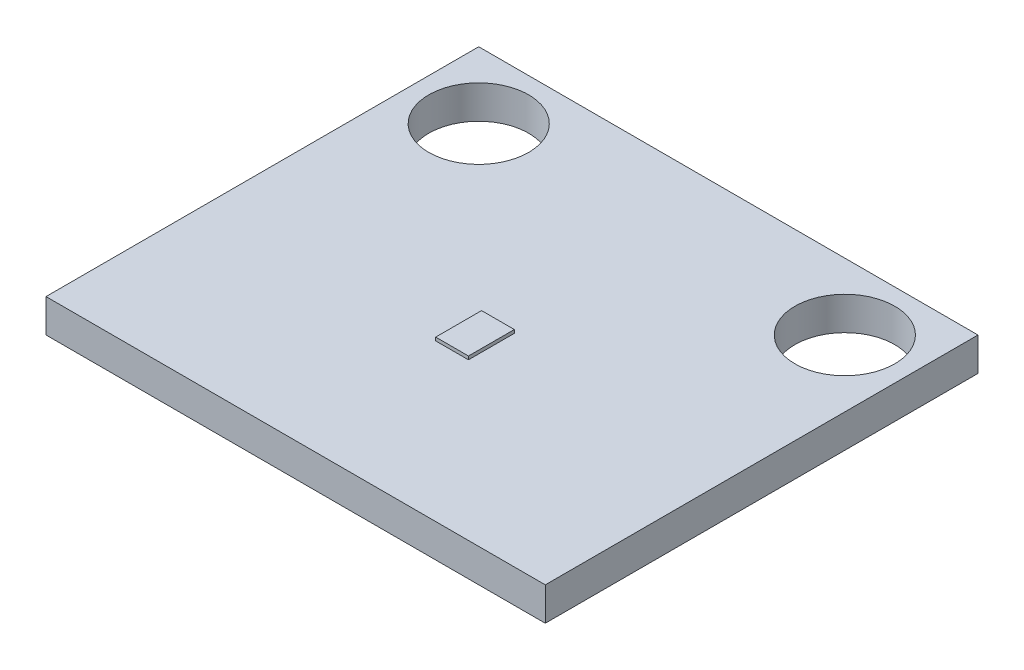
SolidWorks part; units mm, degrees
ref_plane "Front Plane" through (0, 0, 0) normal (0, 0, 1) x (1, 0, 0)
ref_plane "Top Plane" through (0, 0, 0) normal (0, 1, 0) x (1, 0, 0)
ref_plane "Right Plane" through (0, 0, 0) normal (1, 0, 0) x (0, 0, -1)
sketch "Sketch1" plane through (0, 0, 0) normal (0, 1, 0) x (1, 0, 0)
  line L1 (-7.6418, 7.2172) -> (11.4082, 7.2172)
  line L2 (-7.6418, 7.2172) -> (-7.6418, -9.2928)
  line L3 (-7.6418, -9.2928) -> (11.4082, -9.2928)
  line L4 (11.4082, 7.2172) -> (11.4082, -9.2928)
  dimension "D1" = 16.51
  dimension "D2" = 19.05
extrude "Boss-Extrude1" add sketch "Sketch1" along normal blind 1.27 contours L2 L3 L4 L1
sketch "Sketch2" plane through (0, 1.27, 0) normal (0, 1, 0) x (1, 0, 0)
  line L0 (-7.6418, 7.2172) -> (-7.6418, -9.2928) construction
  line L1 (-7.6418, -9.2928) -> (11.4082, -9.2928) construction
  circle A0 centre (-5.1018, 4.6772) radius 1.905
  circle A1 centre (8.8682, 4.6772) radius 1.905
  point P4 (0, 0)
  dimension "D4" = 3.81
  dimension "D1" = 2.54
  dimension "D2" = 13.97
  dimension "D3" = 13.97
extrude "Cut-Extrude1" cut sketch "Sketch2" against normal blind 1.27
sketch "Sketch3" plane through (0, 1.27, 0) normal (0, 1, 0) x (1, 0, 0)
  line L0 (1.8832, 7.2172) -> (1.8832, -9.2928) construction
  line L1 (1.2582, -1.5738) -> (2.5082, -1.5738)
  line L2 (1.2582, -1.5738) -> (1.2582, -3.3238)
  line L3 (1.2582, -3.3238) -> (2.5082, -3.3238)
  line L4 (2.5082, -1.5738) -> (2.5082, -3.3238)
  line L5 (-7.6418, 7.2172) -> (11.4082, 7.2172) construction
  line L6 (-7.6418, -9.2928) -> (11.4082, -9.2928) construction
  point P10 (1.8832, -1.5738)
  dimension "D1" = 1.75
  dimension "D2" = 1.25
  dimension "D3" = 5.969
extrude "Boss-Extrude2" add sketch "Sketch3" along normal blind 0.127
